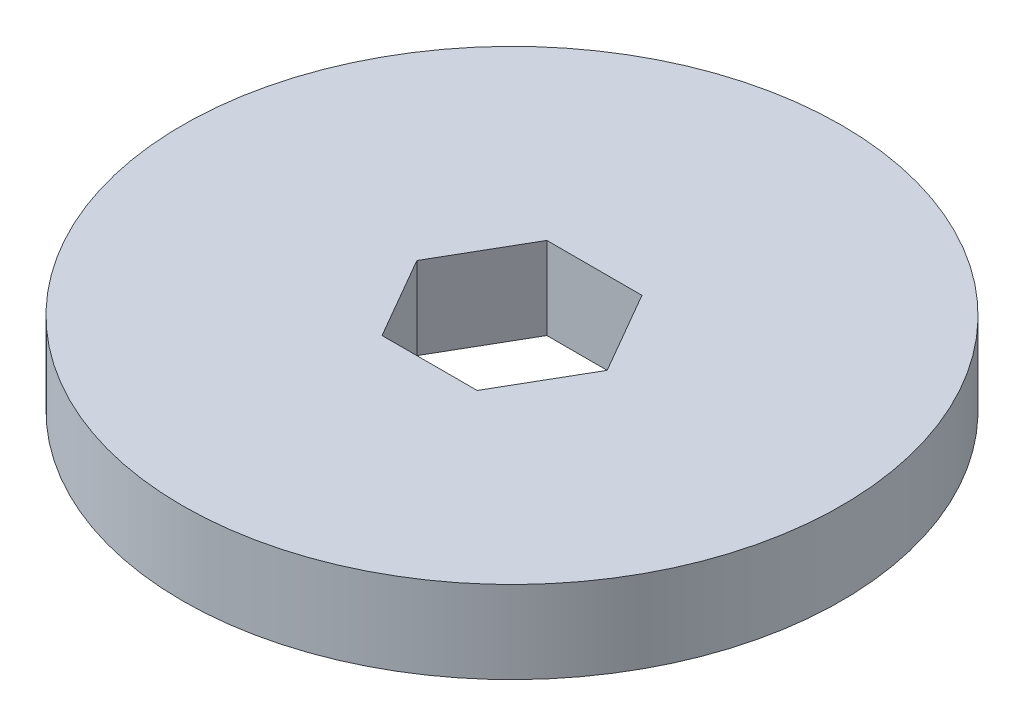
SolidWorks part; units mm, degrees
ref_plane "Front" through (0, 0, 0) normal (0, 0, 1) x (1, 0, 0)
ref_plane "Top" through (0, 0, 0) normal (0, 1, 0) x (1, 0, 0)
ref_plane "Right" through (0, 0, 0) normal (1, 0, 0) x (0, 0, -1)
sketch "Sketch1" plane through (0, 0, 0) normal (0, 1, 0) x (1, 0, 0)
  line L1 (7.3323, 0) -> (3.6662, 6.35)
  line L2 (3.6662, 6.35) -> (-3.6662, 6.35)
  line L3 (-3.6662, 6.35) -> (-7.3323, 0)
  line L4 (-7.3323, 0) -> (-3.6662, -6.35)
  line L5 (-3.6662, -6.35) -> (3.6662, -6.35)
  line L6 (3.6662, -6.35) -> (7.3323, 0)
  circle A0 centre (0, 0) radius 6.35 construction
  circle A1 centre (0, 0) radius 25.4
extrude "Boss-Extrude1" add sketch "Sketch1" along normal blind 6.35
sketch "Sketch2" plane through (0, 6.35, 0) normal (0, 1, 0) x (1, 0, 0)
  line L0 (0, 6.35) -> (0, -6.35) construction
  line L1 (3.6662, 6.35) -> (-3.6662, 6.35) construction
  line L2 (-3.6662, -6.35) -> (3.6662, -6.35) construction
  line L3 (0, 0) -> (7.3323, 0) construction
